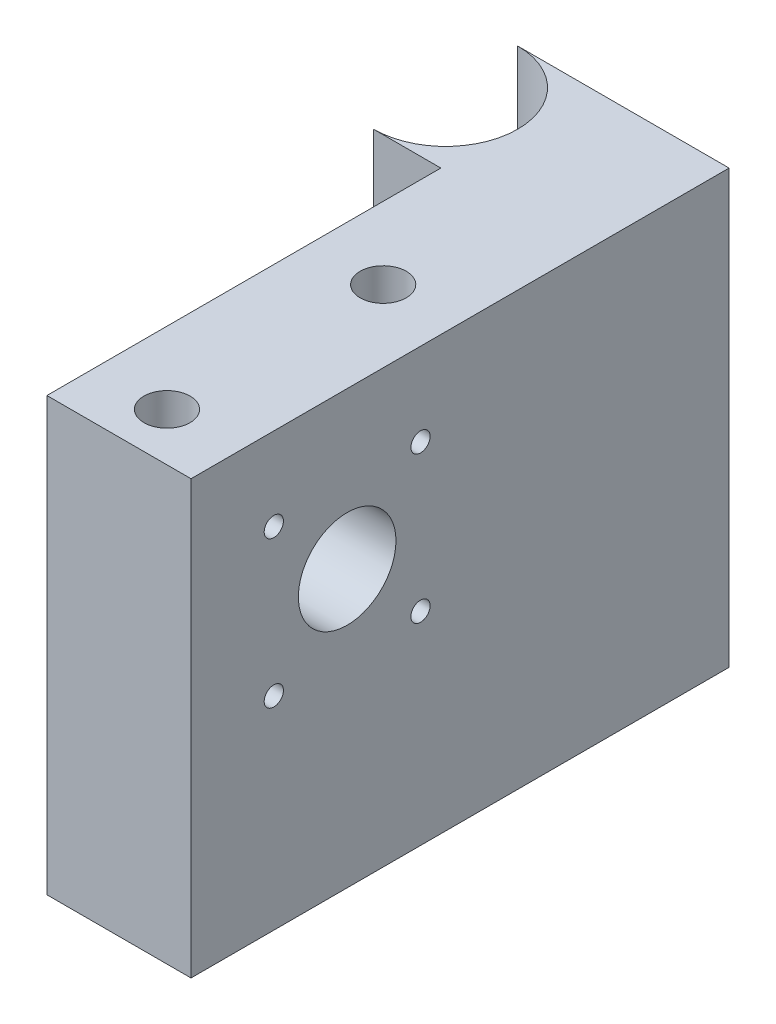
SolidWorks part; units mm, degrees
ref_plane "Front Plane" through (0, 0, 0) normal (0, 0, 1) x (1, 0, 0)
ref_plane "Top Plane" through (0, 0, 0) normal (0, 1, 0) x (1, 0, 0)
ref_plane "Right Plane" through (0, 0, 0) normal (1, 0, 0) x (0, 0, -1)
sketch "Sketch1" plane through (0, 0, 0) normal (0, 1, 0) x (1, 0, 0)
  line L0 (-14.5, 51) -> (7.5, 51)
  line L1 (7.5, 51) -> (7.5, -5)
  line L2 (7.5, -5) -> (-7.5, -5)
  line L3 (-7.5, -5) -> (-7.5, 36)
  line L4 (-7.5, 36) -> (-14.5, 36)
  line L5 (0, 0) -> (0, -5) construction
  circle A0 centre (0, 22.5) radius 2.4
  circle A1 centre (0, 0) radius 2.4
  arc A2 (-14.5, 36) -> (-14.5, 51) centre (-14.5, 43.5) ccw
  dimension "D2" = 4.8
  dimension "D3" = 15
  dimension "D1" = 22.5
  dimension "D4" = 14.5
  dimension "D5" = 21
  dimension "D6" = 15
  dimension "D7" = 5
extrude "Boss-Extrude1" add sketch "Sketch1" along normal blind 45
sketch "Sketch2" plane through (7.5, 0, 0) normal (1, 0, 0) x (0, 0, -1)
  line L0 (3.617, 36.383) -> (18.883, 21.117) construction
  line L1 (3.617, 36.383) -> (18.883, 36.383) construction
  line L2 (3.617, 36.383) -> (3.617, 21.117) construction
  line L3 (3.617, 21.117) -> (18.883, 21.117) construction
  line L4 (18.883, 36.383) -> (18.883, 21.117) construction
  line L5 (-5, 45) -> (-5, 0) construction
  line L7 (-5, 45) -> (51, 45) construction
  circle A0 centre (11.25, 28.75) radius 5.08
  circle A1 centre (3.617, 36.383) radius 1
  circle A2 centre (18.883, 36.383) radius 1
  circle A3 centre (18.883, 21.117) radius 1
  circle A4 centre (3.617, 21.117) radius 1
  dimension "D1" = 10.16
  dimension "D3" = 2
  dimension "D5" = 16.25
  dimension "D2" = 15.266
  dimension "D4" = 16.25
extrude "Cut-Extrude1" cut sketch "Sketch2" against normal up to next
